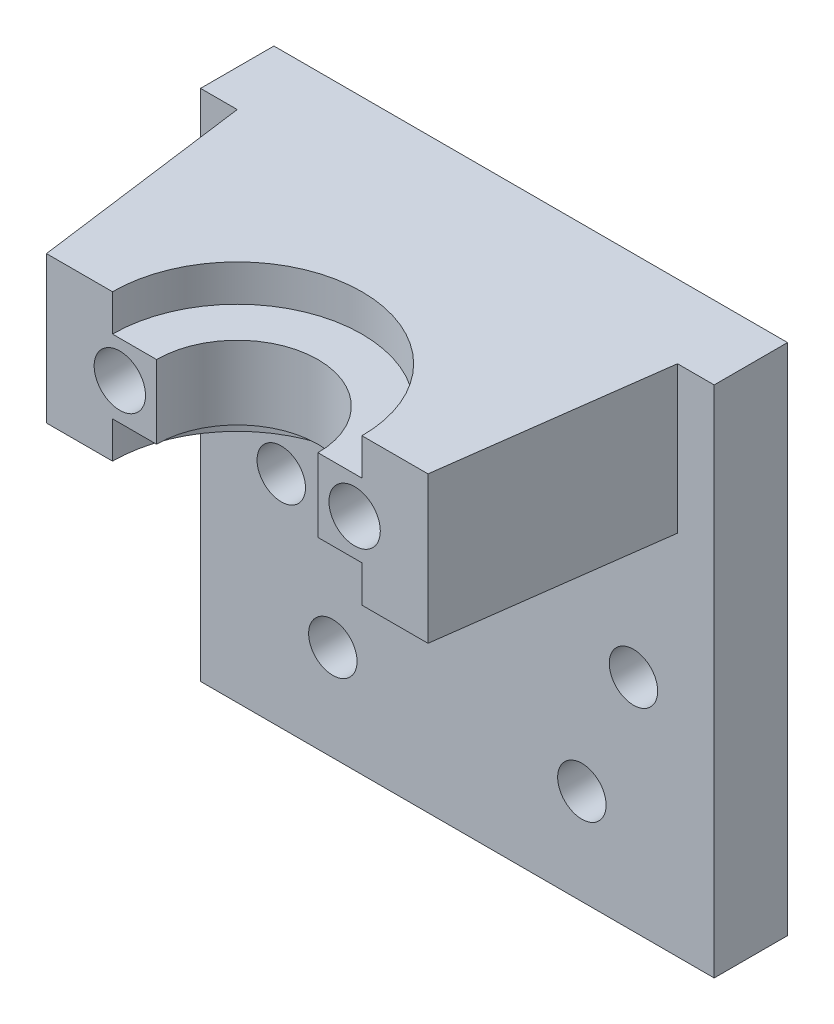
SolidWorks part; units mm, degrees
ref_plane "Plano frontal" through (0, 0, 0) normal (0, 0, 1) x (1, 0, 0)
ref_plane "Plano superior" through (0, 0, 0) normal (0, 1, 0) x (1, 0, 0)
ref_plane "Plano direito" through (0, 0, 0) normal (1, 0, 0) x (0, 0, -1)
sketch "Esboço1" plane through (0, 0, 0) normal (0, 0, 1) x (1, 0, 0)
  line L1 (-25, 25) -> (25, 25)
  line L2 (-25, 25) -> (-25, -25)
  line L3 (-25, -25) -> (25, -25)
  line L4 (25, 25) -> (25, -25)
  line L5 (-25, 25) -> (25, -25) construction
  line L6 (-25, -25) -> (25, 25) construction
  circle A0 centre (12, 0) radius 1.65
  circle A1 centre (8.4853, -8.4853) radius 1.65
  circle A3 centre (-8.4853, -8.4853) radius 1.65
  circle A4 centre (-12, 0) radius 1.65
  circle A5 centre (-8.4853, 8.4853) radius 1.65
  circle A7 centre (8.4853, 8.4853) radius 1.65
  circle A13 centre (0, 12) radius 1.65 [skipped]
  circle A14 centre (0, -12) radius 1.65 [skipped]
  point P0 (0, 0)
  point P8 (14.2307, 2.286)
  point P11 (0, 0)
  point P24 (0, 0)
  point P25 (0, 0)
  point P26 (12, 0)
  dimension "D3" = 3.3
  dimension "D1" = 50
  dimension "D2" = 50
  dimension "D4" = 12
  dimension "D5" = 8
extrude "Ressalto-extrusão1" add sketch "Esboço1" along normal blind 5
sketch "Esboço2" plane through (0, 0, 0) normal (0, 1, 0) x (1, 0, 0)
  line L0 (13, -20) -> (15, -5)
  line L1 (25, -5) -> (-25, -5) construction
  line L2 (15, -5) -> (-15, -5)
  line L3 (-15, -5) -> (-13, -20)
  line L4 (-13, -20) -> (-5.5, -20)
  line L5 (5.5, -20) -> (13, -20)
  arc A0 (5.5, -20) -> (-5.5, -20) centre (0, -20) ccw
  point P1 (0, 0)
  point P3 (0, 0)
  point P10 (0, -5)
  dimension "D2" = 5.5
  dimension "D1" = 26
  dimension "D3" = 15
  dimension "D4" = 30
extrude "Ressalto-extrusão2" add sketch "Esboço2" along normal mid plane 10 from offset 15
sketch "Esboço4" plane through (0, 0, 0) normal (1, 0, 0) x (0, 0, -1)
  line L0 (-20, 20) -> (-11.5, 20)
  line L1 (-20, 20) -> (-5, 20) construction
  line L2 (-11.5, 20) -> (-11.5, 17.5)
  line L3 (-11.5, 17.5) -> (-20, 17.5)
  line L4 (-20, 20) -> (-20, 10) construction
  line L5 (-20, 17.5) -> (-20, 20)
  line L6 (-20, 15) -> (-23.0389, 15) construction
  line L7 (-20, 12.5) -> (-20, 10)
  line L8 (-11.5, 12.5) -> (-20, 12.5)
  line L9 (-11.5, 10) -> (-11.5, 12.5)
  line L10 (-20, 10) -> (-11.5, 10)
  line L11 (-20, 20) -> (-20, -14.7203) construction
  dimension "D1" = 5
  dimension "D2" = 8.5
revolve "Corte-Revolução3" cut sketch "Esboço4" angle 360 about L11
sketch "Esboço5" plane through (0, 0, 5) normal (0, 0, 1) x (1, 0, 0)
  line L1 (-17.5, -15) -> (17.5, -15)
  line L2 (-17.5, -15) -> (-17.5, 20)
  line L3 (-17.5, 20) -> (17.5, 20)
  line L4 (17.5, -15) -> (17.5, 20)
  line L5 (-17.5, -15) -> (17.5, 20) construction
  line L6 (-17.5, 20) -> (17.5, -15) construction
  line L7 (15, 20) -> (-15, 20) construction
  line L9 (-25, 25) -> (25, 25)
  line L10 (-25, 25) -> (-25, -25)
  line L11 (-25, -25) -> (25, -25)
  line L12 (25, 25) -> (25, -25)
  point P0 (0, 2.5)
  dimension "D1" = 15
  dimension "D2" = 35
extrude "Corte-extrusão1" cut sketch "Esboço5" against normal through all both and the other way through all
sketch "Esboço6" plane through (0, 0, 20) normal (0, 0, 1) x (1, 0, 0)
  line L0 (0, 0) -> (0, 20.7373) construction
  line L1 (-5.5, 17.5) -> (-5.5, 12.5) construction
  circle A0 centre (-8, 15) radius 1.75
  circle A1 centre (8, 15) radius 1.75
  point P7 (0, 0)
  point P8 (0, 0)
  point P11 (-5.5, 15)
  point P12 (-9.0864, 15)
  dimension "D1" = 3.5
  dimension "D2" = 16
extrude "Corte-extrusão2" cut sketch "Esboço6" against normal through all
